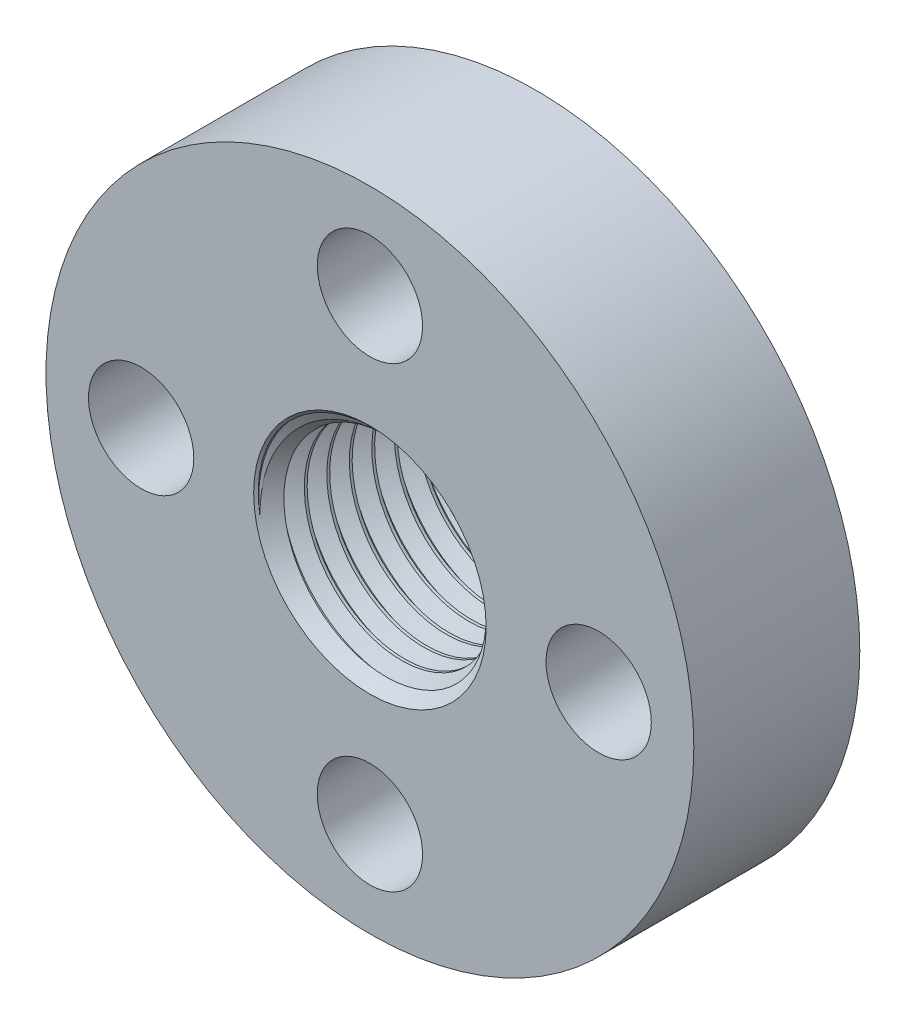
SolidWorks part; units mm, degrees
material "AISI 1015 Steel, Cold Drawn (SS)"
ref_plane "Front" through (0, 0, 0) normal (0, 0, 1) x (1, 0, 0)
ref_plane "Top" through (0, 0, 0) normal (0, 1, 0) x (1, 0, 0)
ref_plane "Right" through (0, 0, 0) normal (1, 0, 0) x (0, 0, -1)
sketch "Sketch1" plane through (0, 0, 0) normal (0, 0, 1) x (1, 0, 0)
  line L0 (0, 0) -> (0, 14.351) construction
  circle A0 centre (0, 0) radius 20.32
  circle A1 centre (0, 0) radius 7.1501 construction
  circle A2 centre (0, 0) radius 14.351 construction
  circle A3 centre (0, 14.351) radius 3.302 construction
  circle A4 centre (0, 0) radius 7.2931 construction
  dimension "E" = 40.64
  dimension "G" = 28.702
  dimension "Thread-Dia" = 14.3002
  dimension "Mounting-Hole" = 6.604
  dimension "D1" = 14.5862
extrude "Boss-Extrude1" add sketch "Sketch1" along normal blind 10.414
sketch "Sketch2" plane through (0, 0, 0) normal (0, 0, 1) x (1, 0, 0)
  circle A0 centre (0, 0) radius 7.1501 construction
  circle A1 centre (0, 0) radius 7.1501
extrude "Boss-Extrude2" add sketch "Sketch2" along normal up to surface (10.414 mm away) separate body up to face at (20.32, 0, 10.414)
sketch "Sketch3" plane through (0, 0, 0) normal (1, 0, 0) x (0, 0, -1)
  line L0 (0, 0) -> (1.4111, 0) construction
  line L1 (0, 7.1501) -> (1.2347, 7.1501)
  line L2 (1.2347, 7.1501) -> (0.7056, 6.2336)
  line L3 (0.7056, 6.2336) -> (0.5292, 6.2336)
  line L4 (0.5292, 6.2336) -> (0, 7.1501)
  line L5 (0.6174, 7.1501) -> (0.6174, 6.2336) construction
  line L6 (0.2646, 6.6918) -> (0.9701, 6.6918) construction
  dimension "Pitch" = 1.4111
  dimension "D1" = 0.7056
  dimension "D2" = 0.1764
  dimension "D3" = 60
sketch "Sketch4" plane through (0, 0, 0) normal (0, 0, 1) x (1, 0, 0)
  circle A0 centre (0, 0) radius 7.1501 construction
  circle A1 centre (0, 0) radius 7.1501
curve "Helix/Spiral1" pitch 1.4111 height 13.589 radius 7.1501 centre (0, 0, 0) axis (0, 0, 1) start towards (0.7071, 0.7071, 0) parameters "Lead"=1.4111
sketch "Sketch5" plane through (0, 0, 0) normal (0, 0, 1) x (1, 0, 0)
  circle A0 centre (0, 14.351) radius 3.302 construction
  circle A1 centre (0, 14.351) radius 3.302
extrude "Cut-Extrude1" cut sketch "Sketch5" along normal up to surface (10.414 mm away) up to face at (20.32, 0, 10.414)
ref_axis "Axis1" through (0, 0, 10.414) along (0, 0, -1)
pattern_circular "CirPattern1" count 4 over 360 about axis through (0, 0, 10.414) along (0, 0, -1) of "Cut-Extrude1"
sweep "Cut-Sweep1" cut profiles "Sketch3" path "Helix/Spiral1" align with end faces yes
combine bodies "Combine1" operation type subtract main body 113 bodies to subtract 111
ref_plane "Plane1" through (0, 0, 5.207) normal (0, 0, -1) x (-1, 0, 0)
sketch "Sketch6" plane through (0, 0, 0) normal (0, 0, 1) x (1, 0, 0)
  circle A0 centre (0, 0) radius 7.2931 construction
  circle A1 centre (0, 0) radius 7.2931
extrude "Cut-Extrude2" cut sketch "Sketch6" along normal blind 2.54 draft 45
mirror "Mirror1" about plane through (0, 0, 5.207) normal (0, 0, -1) of "Cut-Extrude2"
sketch "Sketch7" plane through (0, 0, 0) normal (0, 0, 1) x (1, 0, 0)
  circle A0 centre (0, 0) radius 14.351 construction
  circle A1 centre (0, 0) radius 14.351 construction
equation "\"D1@Sketch3\" = \"Pitch@Sketch3\"/2"
equation "\"D1@Sketch1\" = \"Thread-Dia@Sketch1\"*1.02"
equation "\"D2@Sketch3\" = \"Pitch@Sketch3\"/8"
equation "\"D3@Helix/Spiral1\" = \"F@Boss-Extrude1\"+.125"
